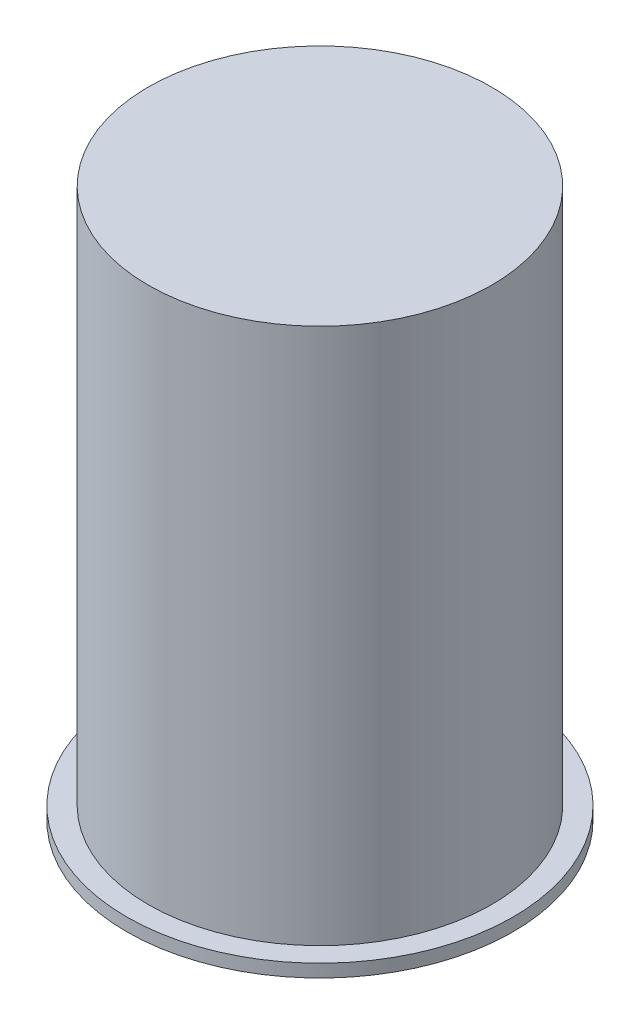
SolidWorks part; units mm, degrees
ref_plane "Front Plane" through (0, 0, 0) normal (0, 0, 1) x (1, 0, 0)
ref_plane "Top Plane" through (0, 0, 0) normal (0, 1, 0) x (1, 0, 0)
ref_plane "Right Plane" through (0, 0, 0) normal (1, 0, 0) x (0, 0, -1)
sketch "Sketch1" plane through (0, 0, 0) normal (0, 1, 0) x (1, 0, 0)
  circle A0 centre (0, 0) radius 4.5
  dimension "D1" = 9
extrude "Boss-Extrude1" add sketch "Sketch1" along normal blind 0.3
dome "Dome1" faces to dome 1 distance 1 reverse direction no elliptical dome no face at (0, 0, 4.5) parameters "D1"=1
sketch "Sketch2" plane through (0, 0.3, 0) normal (0, 1, 0) x (1, 0, 0)
  circle A0 centre (0, 0) radius 4
  dimension "D1" = 8
extrude "Boss-Extrude2" add sketch "Sketch2" along normal blind 12.5
